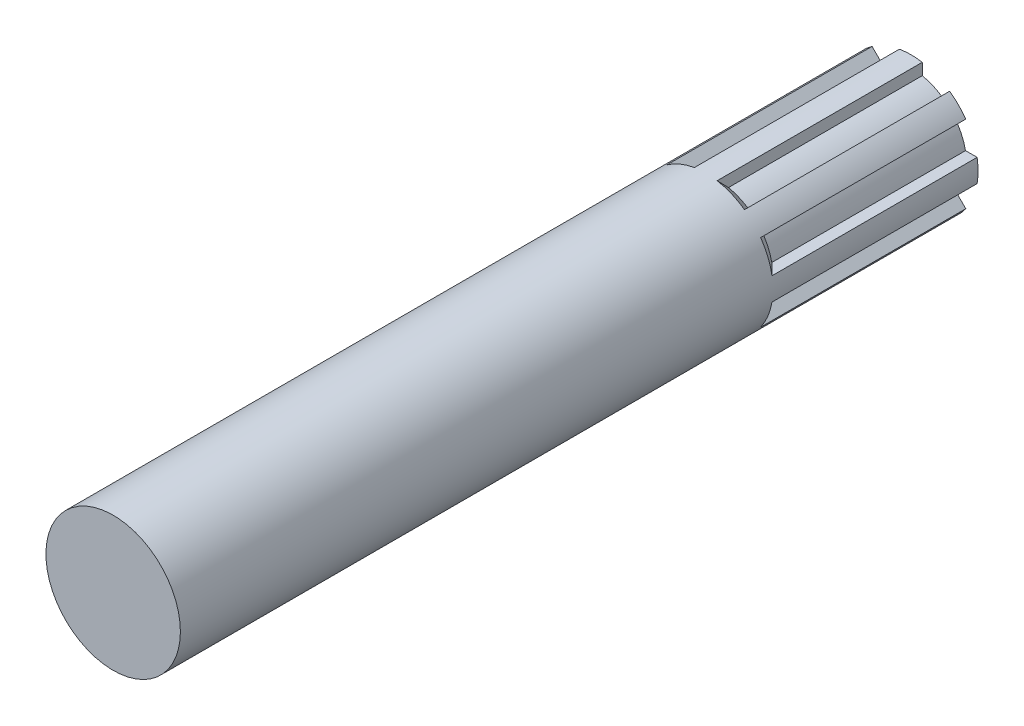
SolidWorks part; units mm, degrees
material "Cast Stainless Steel"
ref_plane "Front Plane" through (0, 0, 0) normal (0, 0, 1) x (1, 0, 0)
ref_plane "Top Plane" through (0, 0, 0) normal (0, 1, 0) x (1, 0, 0)
ref_plane "Right Plane" through (0, 0, 0) normal (1, 0, 0) x (0, 0, -1)
sketch "Sketch1" plane through (0, 0, 0) normal (0, 0, 1) x (1, 0, 0)
  circle A0 centre (0, 0) radius 2.95
  dimension "D1" = 5.9
extrude "Boss-Extrude1" add sketch "Sketch1" along normal blind 35
sketch "Sketch2" plane through (0, 0, 0) normal (0, 0, -1) x (-1, 0, 0)
  line L0 (0, 2.95) -> (0, -2.95) construction
  line L1 (-0.5, 2.3984) -> (-0.5, 2.9073)
  line L2 (0.5, 2.3984) -> (0.5, 2.9073)
  line L3 (1.3424, 2.0495) -> (1.7022, 2.4093)
  line L4 (2.0495, 1.3424) -> (2.4093, 1.7022)
  line L5 (2.3984, 0.5) -> (2.9073, 0.5)
  line L6 (2.3984, -0.5) -> (2.9073, -0.5)
  line L7 (2.0495, -1.3424) -> (2.4093, -1.7022)
  line L8 (1.3424, -2.0495) -> (1.7022, -2.4093)
  line L9 (0.5, -2.3984) -> (0.5, -2.9073)
  line L10 (-0.5, -2.3984) -> (-0.5, -2.9073)
  line L11 (-1.3424, -2.0495) -> (-1.7022, -2.4093)
  line L12 (-2.0495, -1.3424) -> (-2.4093, -1.7022)
  line L13 (-2.3984, -0.5) -> (-2.9073, -0.5)
  line L14 (-2.3984, 0.5) -> (-2.9073, 0.5)
  line L15 (-2.0495, 1.3424) -> (-2.4093, 1.7022)
  line L16 (-1.3424, 2.0495) -> (-1.7022, 2.4093)
  circle A0 centre (0, 0) radius 2.45
  circle A1 centre (0, 0) radius 2.95
  circle A2 centre (0, 0) radius 2.95
  circle A3 centre (0, 0) radius 2.45
  circle A4 centre (0, 0) radius 2.95
  circle A5 centre (0, 0) radius 2.45
  circle A6 centre (0, 0) radius 2.95
  circle A7 centre (0, 0) radius 2.45
  circle A8 centre (0, 0) radius 2.95
  circle A9 centre (0, 0) radius 2.45
  circle A10 centre (0, 0) radius 2.95
  circle A11 centre (0, 0) radius 2.45
  circle A12 centre (0, 0) radius 2.95
  circle A13 centre (0, 0) radius 2.45
  circle A14 centre (0, 0) radius 2.95
  circle A15 centre (0, 0) radius 2.45
  circle A16 centre (0, 0) radius 2.95
  point P54 (0, 0)
  circle M5 centre (0, 0) radius 2.95
  dimension "D2" = 0.5
  dimension "D3" = 1
  dimension "D1" = 0
  dimension "D4" = 8
extrude "Cut-Extrude1" cut sketch "Sketch2" against normal blind 8 contours A0 L15 L14 M5 | A0 L1 L16 M5 | A0 L3 L2 M5 | A0 L5 L4 M5 | A0 L7 L6 M5 | A0 L9 L8 M5 | A0 L11 L10 M5 | A0 L13 L12 M5 region at (1.0314, 2.4901, 0) region at (-1.0314, 2.4901, 0) region at (2.4901, 1.0314, 0) region at (-2.4901, 1.0314, 0) region at (2.4901, -1.0314, 0) region at (-2.4901, -1.0314, 0) region at (1.0314, -2.4901, 0) region at (-1.0314, -2.4901, 0)
chamfer "Chamfer1" distance 1 angle 45 8 edges at (-1.1289, -2.7254, 8) (-2.7254, -1.1289, 8) (-2.7254, 1.1289, 8) (-1.1289, 2.7254, 8) (1.1289, -2.7254, 8) (2.7254, -1.1289, 8) (2.7254, 1.1289, 8) (1.1289, 2.7254, 8)
sketch3d "3DSketch1"
  line L0 (0, 0, 0) -> (0, 0, 35)
  line L1 (0, 0, 35) -> (0, 0, 9) construction
